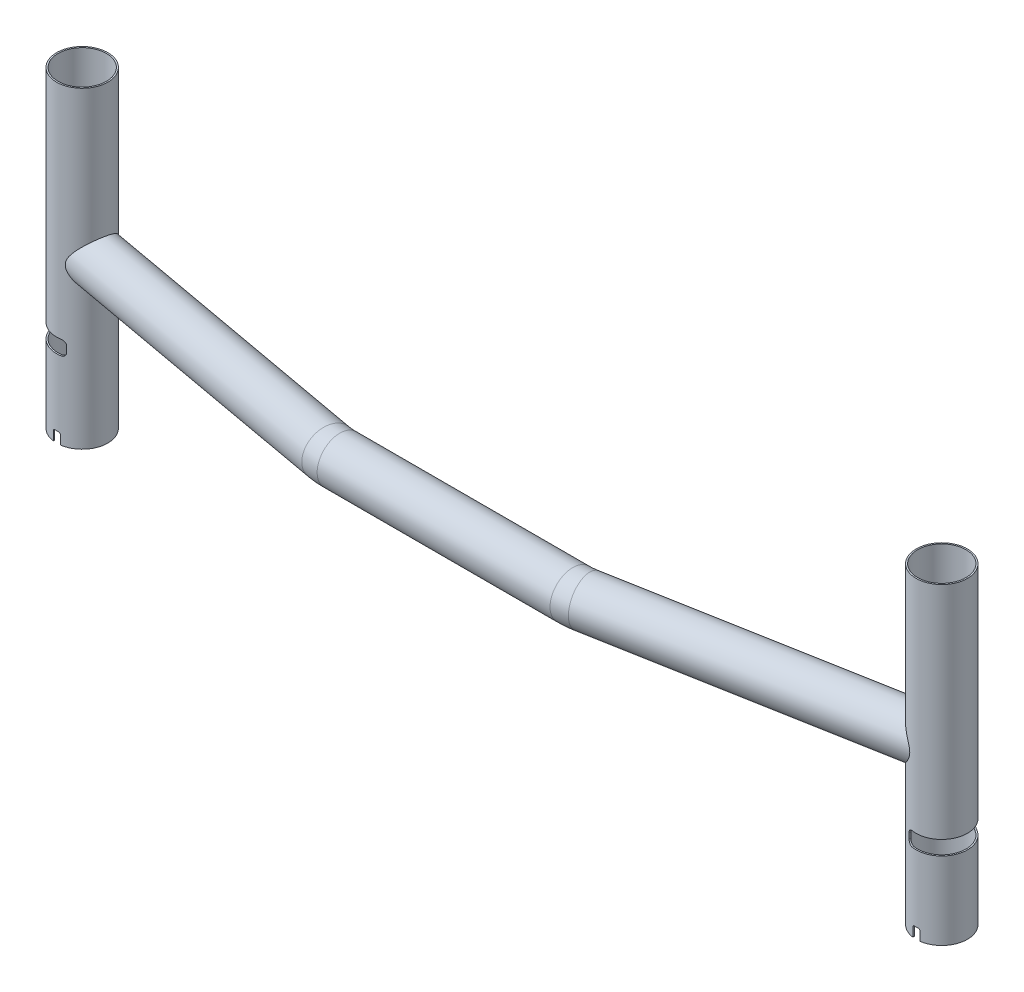
SolidWorks part; units mm, degrees
ref_plane "Front Plane" through (0, 0, 0) normal (0, 0, 1) x (1, 0, 0)
ref_plane "Top Plane" through (0, 0, 0) normal (0, 1, 0) x (1, 0, 0)
ref_plane "Right Plane" through (0, 0, 0) normal (1, 0, 0) x (0, 0, -1)
sketch "Sketch1" plane through (0, 0, 0) normal (0, 1, 0) x (1, 0, 0)
  line L0 (0, 0) -> (0, 107.988) construction
  line L1 (-65, 0) -> (65, 0)
  line L2 (72.1386, 0.6421) -> (234, 30)
  line L3 (-72.1386, 0.6421) -> (-234, 30)
  arc A0 (72.1386, 0.6421) -> (65, 0) centre (65, 40) cw
  arc A1 (-72.1386, 0.6421) -> (-65, 0) centre (-65, 40) ccw
  dimension "D2" = 40
  dimension "D1" = 234
  dimension "D3" = 65
  dimension "D4" = 30
ref_plane "Plane1" through (234, 0, -30) normal (0.9839, 0, -0.1785) x (-0.1785, 0, -0.9839)
sketch "Sketch2" plane through (234, 0, -30) normal (0.9839, 0, -0.1785) x (-0.1785, 0, -0.9839)
  line L0 (0.6421, 0) -> (0, 0) construction
  circle A0 centre (0, 0) radius 12.7
  circle A1 centre (0, 0) radius 11.9
  dimension "D1" = 0.8
  dimension "D2" = 25.4
sweep "Sweep1" add profiles "Sketch2" path "Sketch1"
sketch "Sketch3" plane through (0, 0, 0) normal (0, 1, 0) x (1, 0, 0)
  line L0 (231.7335, 42.4961) -> (236.2665, 17.5039) construction
  line L1 (231.7335, 42.4961) -> (234, 30) construction
  line L2 (234, 30) -> (239.9037, 31.0708) construction
  circle A0 centre (239.9037, 31.0708) radius 14.3
  circle A1 centre (239.9037, 31.0708) radius 13.5
  dimension "D1" = 0.8
  dimension "D3" = 28.6
  dimension "D4" = 0.8
  dimension "D2" = 6
extrude "Boss-Extrude1" add sketch "Sketch3" along normal blind 86.5 and the other way blind 88
sketch "Sketch4" plane through (0, -88, 0) normal (0, -1, 0) x (1, 0, 0)
  circle A0 centre (239.9037, -31.0708) radius 13.5
  dimension "D1" = 27
extrude "Cut-Extrude1" cut sketch "Sketch4" against normal through all
sketch "Sketch5" plane through (234, 0, -30) normal (0.9839, 0, -0.1785) x (-0.1785, 0, -0.9839)
  circle A0 centre (-0.0149, 0) radius 11.9
  dimension "D1" = 23.8
extrude "Cut-Extrude2" cut sketch "Sketch5" against normal blind 88
sketch "Sketch6" plane through (0, 86.5, 0) normal (0, 1, 0) x (1, 0, 0)
  line L0 (239.9037, 31.0708) -> (72.1386, 0.6421)
  line L1 (69.8721, 13.1383) -> (74.4051, -11.854) construction
  line L2 (239.9037, 31.0708) -> (244.4588, 43.7791)
  circle A0 centre (239.9037, 31.0708) radius 13.5 construction
  dimension "D1" = 60
ref_plane "Plane2" through (239.9037, 86.5, -31.0708) normal (0.3374, 0, -0.9414) x (-0.9414, 0, -0.3374)
sketch "Sketch7" plane through (239.9037, 86.5, -31.0708) normal (0.3374, 0, -0.9414) x (-0.9414, 0, -0.3374)
  line L0 (0, -174.5) -> (0, -125.7306) construction
  line L1 (-14.3, -174.5) -> (14.3, -174.5) construction
  line L2 (-12.7, -123.2306) -> (-27.4942, -123.2306)
  line L3 (-27.4942, -123.2306) -> (-27.4942, -131.2306)
  line L4 (-2.5, -123.2306) -> (-12.7, -123.2306)
  line L5 (-2.5, -131.2306) -> (-12.7, -131.2306)
  line L7 (0, -125.7306) -> (0, -128.7306)
  line L8 (-27.4942, -131.2306) -> (-12.7, -131.2306)
  arc A0 (0, -125.7306) -> (-2.5, -123.2306) centre (-2.5, -125.7306) ccw
  arc A1 (0, -128.7306) -> (-2.5, -131.2306) centre (-2.5, -128.7306) cw
  dimension "D1" = 2.5
  dimension "D2" = 48.7694
extrude "Cut-Extrude3" cut sketch "Sketch7" against normal blind 20 and the other way blind 20
sketch "Sketch9" plane through (0, 0, 0) normal (0, 0, 1) x (1, 0, 0)
  line L0 (225.6037, -88) -> (254.2037, -88) construction
  line L1 (238.9037, -82) -> (240.9037, -82)
  line L2 (237.9037, -83) -> (237.9037, -94)
  line L3 (237.9037, -94) -> (241.9037, -94)
  line L4 (241.9037, -83) -> (241.9037, -94)
  line L5 (237.9037, -82) -> (241.9037, -94) construction
  line L6 (237.9037, -94) -> (241.9037, -82) construction
  arc A0 (241.9037, -83) -> (240.9037, -82) centre (240.9037, -83) ccw
  arc A1 (238.9037, -82) -> (237.9037, -83) centre (238.9037, -83) ccw
  point P0 (239.9037, -88)
  dimension "D3" = 1
  dimension "D1" = 12
  dimension "D2" = 4
extrude "Cut-Extrude5" cut sketch "Sketch9" against normal up to surface (17.7198 mm away) up to face at (239.9037, -88, -17.5708)
mirror "Mirror1" about plane through (0, 0, 0) normal (1, 0, 0) of "Cut-Extrude5", "Cut-Extrude2", "Cut-Extrude3", "Boss-Extrude1", "Cut-Extrude1"
sketch "Sketch8" plane through (0, 0, 0) normal (0, 1, 0) x (1, 0, 0)
  line L0 (72.1386, 0.6421) -> (216.9875, 26.5937) construction
  line L1 (69.8721, 13.1383) -> (74.4051, -11.854) construction
  circle A0 centre (216.9875, 26.5937) radius 3
extrude "Cut-Extrude4" cut sketch "Sketch8" against normal up to next
